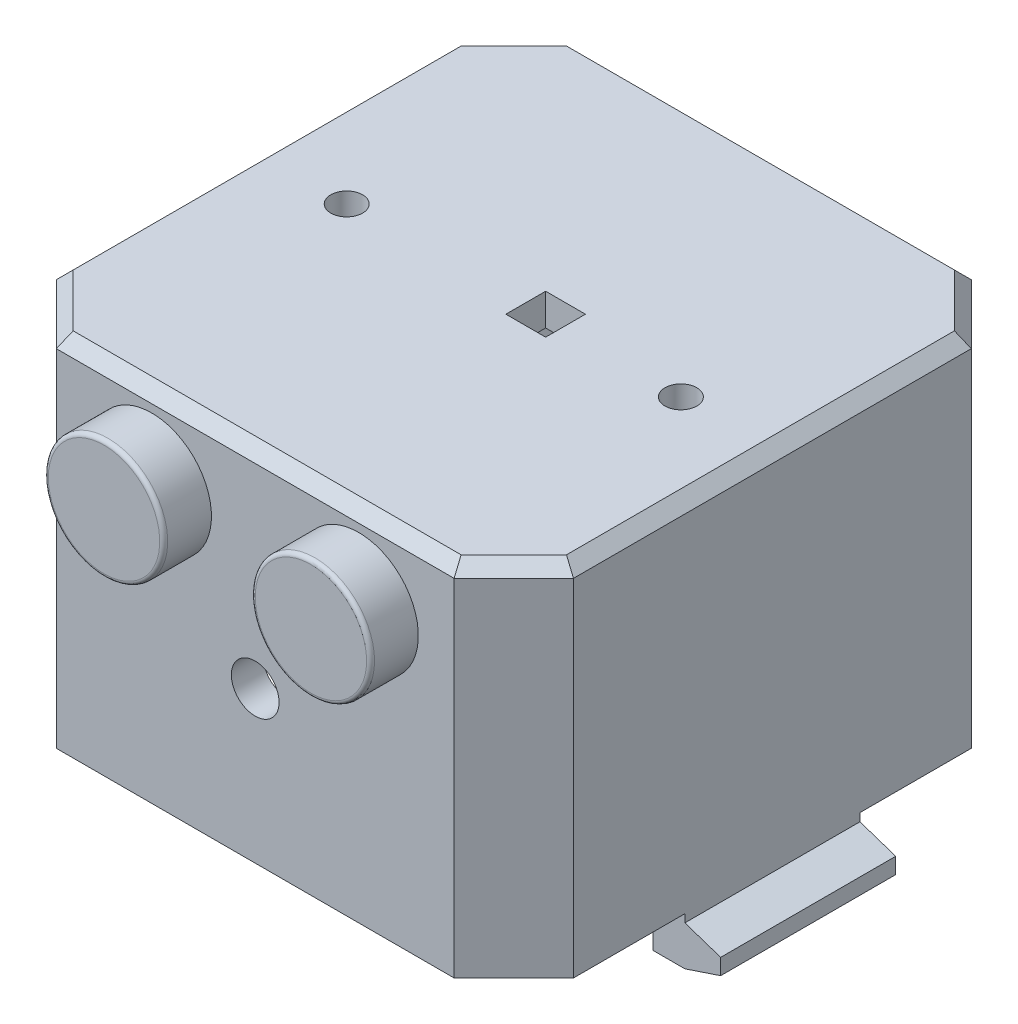
SolidWorks part; units mm, degrees
ref_plane "Alzado" through (0, 0, 0) normal (0, 0, 1) x (1, 0, 0)
ref_plane "Planta" through (0, 0, 0) normal (0, 1, 0) x (1, 0, 0)
ref_plane "Vista lateral" through (0, 0, 0) normal (1, 0, 0) x (0, 0, -1)
sketch "Croquis1" plane through (0, 0, 0) normal (0, 1, 0) x (1, 0, 0)
  line L1 (-25, -32.5) -> (25, -32.5)
  line L3 (-25, 32.5) -> (25, 32.5)
  line L5 (-25, -32.5) -> (25, 32.5) construction
  line L6 (-25, 32.5) -> (25, -32.5) construction
  line L10 (32.5, 25) -> (32.5, -25)
  line L11 (25, -32.5) -> (32.5, -25)
  line L12 (32.5, 25) -> (25, 32.5)
  line L13 (-32.5, 25) -> (-32.5, -25)
  line L14 (-32.5, -25) -> (-25, -32.5)
  line L15 (-32.5, 25) -> (-25, 32.5)
  point P0 (0, 0)
  point P10 (0, 32.5)
  dimension "D1" = 65
  dimension "D2" = 65
  dimension "D3" = 50
  dimension "D4" = 50
  dimension "D5" = 25
  dimension "D6" = 25
extrude "Saliente-Extruir1" add sketch "Croquis1" along normal blind 45
shell "Vaciado2" thickness 4 removed face at (0, 0, 0)
chamfer "Chaflán3" distance 1.5 angle 45 8 edges at (0, 45, -32.5) (32.5, 45, 0) (0, 45, 32.5) (-32.5, 45, 0) (-28.75, 45, 28.75) (28.75, 45, 28.75) (28.75, 45, -28.75) (-28.75, 45, -28.75)
sketch "Croquis2" plane through (0, 0, 32.5) normal (0, 0, 1) x (1, 0, 0)
  line L0 (0, 0) -> (0, 6.916) construction
  circle A0 centre (13, 35) radius 7.5
  circle A1 centre (-13, 35) radius 7.5
  dimension "D1" = 15
  dimension "D2" = 13
  dimension "D3" = 35
extrude "Saliente-Extruir2" add sketch "Croquis2" along normal blind 6
sketch "Croquis4" plane through (0, 0, 28.5) normal (0, 0, -1) x (-1, 0, 0)
  line L0 (0, 0) -> (0, 4.7403) construction
  line L1 (0, 0) -> (0, 6.916) construction
  circle A0 centre (-13, 35) radius 5
  circle A1 centre (13, 35) radius 5
  dimension "D1" = 10
extrude "Cortar-Extruir2" cut sketch "Croquis4" against normal blind 8
fillet "Redondeo1" radius 0.5 2 edges at (-20.5, 35, 38.5) (20.5, 35, 38.5)
sketch "Croquis5" plane through (0, 0, 32.5) normal (0, 0, 1) x (1, 0, 0)
  circle A0 centre (0, 19) radius 3
  dimension "D2" = 6
  dimension "D1" = 19
extrude "Cortar-Extruir3" cut sketch "Croquis5" against normal blind 10
sketch "Croquis13" plane through (0, 0, 36.5) normal (0, 0, -1) x (-1, 0, 0)
  circle A0 centre (-13, 35) radius 2.6
  circle A1 centre (13, 35) radius 2.6
  circle A2 centre (13, 35) radius 5
  circle A3 centre (-13, 35) radius 5
  dimension "D1" = 5.2
  dimension "D2" = 5.2
extrude "Saliente-Extruir8" add sketch "Croquis13" along normal blind 8
sketch "Croquis7" plane through (0, 0, 28.5) normal (0, 0, -1) x (-1, 0, 0)
  line L0 (23.3431, 0) -> (-23.3431, 0) construction
  line L1 (-13.58, 8.5) -> (-9.58, 8.5)
  line L2 (-13.58, 8.5) -> (-13.58, 12.5)
  line L3 (-13.58, 12.5) -> (-9.58, 12.5)
  line L4 (-9.58, 8.5) -> (-9.58, 12.5)
  line L5 (-13.58, 8.5) -> (-9.58, 12.5) construction
  line L6 (-13.58, 12.5) -> (-9.58, 8.5) construction
  line L8 (-13.58, 26) -> (-9.58, 26)
  line L9 (-13.58, 26) -> (-13.58, 30)
  line L10 (-13.58, 30) -> (-9.58, 30)
  line L11 (-9.58, 26) -> (-9.58, 30)
  line L12 (-13.58, 26) -> (-9.58, 30) construction
  line L13 (-13.58, 30) -> (-9.58, 26) construction
  line L14 (13.43, 12.5) -> (9.43, 8.5) construction
  line L15 (13.43, 8.5) -> (9.43, 12.5) construction
  line L16 (9.43, 8.5) -> (9.43, 12.5)
  line L17 (13.43, 12.5) -> (9.43, 12.5)
  line L18 (13.43, 8.5) -> (13.43, 12.5)
  line L19 (13.43, 8.5) -> (9.43, 8.5)
  line L20 (13.43, 30) -> (9.43, 26) construction
  line L21 (13.43, 26) -> (9.43, 30) construction
  line L22 (9.43, 26) -> (9.43, 30)
  line L23 (13.43, 30) -> (9.43, 30)
  line L24 (13.43, 26) -> (13.43, 30)
  line L25 (13.43, 26) -> (9.43, 26)
  point P0 (-11.58, 10.5)
  point P8 (-11.58, 28)
  point P13 (0, 0)
  point P15 (11.43, 10.5)
  point P16 (11.43, 28)
  point P20 (11.43, 10.5)
  point P25 (11.43, 28)
  point P26 (-11.58, 28)
  point P27 (11.43, 28)
  point P28 (11.43, 10.5)
  point P29 (-11.58, 10.5)
  dimension "D1" = 10.5
  dimension "D2" = 4
  dimension "D3" = 4
  dimension "D4" = 11.58
  dimension "D5" = 4
  dimension "D6" = 4
  dimension "D7" = 28
  dimension "D8" = 23.01
  dimension "D9" = 23.01
  dimension "D10" = 4
  dimension "D11" = 4
  dimension "D12" = 4
  dimension "D13" = 4
  dimension "D14" = 10.5
  dimension "D15" = 28
extrude "Saliente-Extruir3" add sketch "Croquis7" along normal blind 1
sketch "Croquis8" plane through (0, 0, 27.5) normal (0, 0, -1) x (-1, 0, 0)
  line L0 (0, 0) -> (0, 4.8013) construction
  line L1 (23.3431, 0) -> (-23.3431, 0) construction
  circle A0 centre (-11.505, 10.4893) radius 2
  circle A1 centre (-11.505, 27.9763) radius 2
  circle A2 centre (11.505, 10.4893) radius 2
  circle A3 centre (11.505, 27.9763) radius 2
  dimension "D1" = 4
  dimension "D2" = 4
  dimension "D3" = 23.01
  dimension "D4" = 23.01
extrude "Saliente-Extruir4" add sketch "Croquis8" along normal blind 1
sketch "Croquis9" plane through (0, 0, 26.5) normal (0, 0, -1) x (-1, 0, 0)
  circle A0 centre (-11.505, 27.9763) radius 1.6
  circle A1 centre (-11.505, 10.4893) radius 1.6
  circle A2 centre (11.505, 10.4893) radius 1.6
  circle A3 centre (11.505, 27.9763) radius 1.6
  dimension "D1" = 3.2
  dimension "D2" = 3.2
  dimension "D3" = 3.2
  dimension "D4" = 3.2
extrude "Cortar-Extruir5" cut sketch "Croquis9" against normal blind 2
sketch "Croquis12" plane through (0, 41, 0) normal (0, -1, 0) x (1, 0, 0)
  line L0 (0, 0) -> (-5.199, 0) construction
  line L1 (-21.9, -8.93) -> (21.9, -8.93) construction
  line L2 (-21.9, -8.93) -> (-21.9, 8.93) construction
  line L3 (-21.9, 8.93) -> (21.9, 8.93) construction
  line L4 (21.9, -8.93) -> (21.9, 8.93) construction
  line L5 (-21.9, -8.93) -> (21.9, 8.93) construction
  line L6 (-21.9, 8.93) -> (21.9, -8.93) construction
  line L7 (0, 0) -> (0, 4.1573) construction
  circle A0 centre (-20.65, 7.68) radius 0.8
  circle A1 centre (-20.65, 7.68) radius 1.15
  circle A2 centre (-20.65, -7.68) radius 1.15
  circle A3 centre (-20.65, -7.68) radius 0.8
  circle A4 centre (20.65, 7.68) radius 1.15
  circle A5 centre (20.65, 7.68) radius 0.8
  circle A6 centre (20.65, -7.68) radius 1.15
  circle A7 centre (20.65, -7.68) radius 0.8
  point P0 (0, 0)
  dimension "D6" = 1.6
  dimension "D4" = 2.3
  dimension "D1" = 43.8
  dimension "D2" = 17.86
  dimension "D3" = 1.25
  dimension "D7" = 1.25
extrude "Saliente-Extruir7" add sketch "Croquis12" along normal blind 6
sketch "Croquis14" plane through (0, 41, 0) normal (0, -1, 0) x (1, 0, 0)
  line L1 (-22.15, 6.43) -> (-19.15, 6.43)
  line L2 (-22.15, 6.43) -> (-22.15, 8.93)
  line L3 (-22.15, 8.93) -> (-19.15, 8.93)
  line L4 (-19.15, 6.43) -> (-19.15, 8.93)
  line L5 (-22.15, 6.43) -> (-19.15, 8.93) construction
  line L6 (-22.15, 8.93) -> (-19.15, 6.43) construction
  line L7 (-22.15, -8.93) -> (-19.15, -8.93)
  line L8 (-22.15, -8.93) -> (-22.15, -6.43)
  line L9 (-22.15, -6.43) -> (-19.15, -6.43)
  line L10 (-19.15, -8.93) -> (-19.15, -6.43)
  line L11 (-22.15, -8.93) -> (-19.15, -6.43) construction
  line L12 (-22.15, -6.43) -> (-19.15, -8.93) construction
  line L13 (19.15, 6.43) -> (22.15, 6.43)
  line L14 (19.15, 6.43) -> (19.15, 8.93)
  line L15 (19.15, 8.93) -> (22.15, 8.93)
  line L16 (22.15, 6.43) -> (22.15, 8.93)
  line L17 (19.15, 6.43) -> (22.15, 8.93) construction
  line L18 (19.15, 8.93) -> (22.15, 6.43) construction
  line L19 (19.15, -8.93) -> (22.15, -8.93)
  line L20 (19.15, -8.93) -> (19.15, -6.43)
  line L21 (19.15, -6.43) -> (22.15, -6.43)
  line L22 (22.15, -8.93) -> (22.15, -6.43)
  line L23 (19.15, -8.93) -> (22.15, -6.43) construction
  line L24 (19.15, -6.43) -> (22.15, -8.93) construction
  point P0 (-20.65, 7.68)
  point P6 (-20.65, -7.68)
  point P12 (20.65, 7.68)
  point P18 (20.65, -7.68)
  dimension "D1" = 3
  dimension "D2" = 2.5
  dimension "D3" = 3
  dimension "D4" = 2.5
  dimension "D5" = 3
  dimension "D6" = 2.5
  dimension "D7" = 3
  dimension "D8" = 2.5
extrude "Saliente-Extruir9" add sketch "Croquis14" along normal blind 5
sketch "Croquis15" plane through (-32.5, 0, 0) normal (-1, 0, 0) x (0, 0, 1)
  line L1 (-6, 40.5) -> (6, 40.5)
  line L2 (-6, 40.5) -> (-6, 32.5)
  line L3 (-6, 32.5) -> (6, 32.5)
  line L4 (6, 40.5) -> (6, 32.5)
  dimension "D1" = 8
  dimension "D2" = 12
  dimension "D3" = 3
  dimension "D4" = 19
extrude "Cortar-Extruir6" cut sketch "Croquis15" against normal blind 7
sketch "Croquis16" plane through (0, 0, -28.5) normal (0, 0, 1) x (1, 0, 0)
  line L2 (18.95, 6.05) -> (6.55, 6.05)
  line L3 (18.95, 6.05) -> (18.95, 18.45)
  line L4 (18.95, 18.45) -> (6.55, 18.45)
  line L5 (6.55, 6.05) -> (6.55, 18.45)
  line L6 (5.5, 5) -> (20, 5)
  line L7 (5.5, 5) -> (5.5, 19.5)
  line L8 (5.5, 19.5) -> (20, 19.5)
  line L9 (20, 5) -> (20, 19.5)
  line L10 (5.5, 5) -> (20, 19.5) construction
  line L11 (5.5, 19.5) -> (20, 5) construction
  line L12 (18.95, 6.05) -> (6.55, 18.45) construction
  line L13 (18.95, 18.45) -> (6.55, 6.05) construction
  point P0 (12.75, 12.25)
  point P4 (12.75, 12.25)
  dimension "D1" = 12.4
  dimension "D2" = 12.4
  dimension "D3" = 5
  dimension "D4" = 5
  dimension "D5" = 14.5
  dimension "D6" = 14.5
extrude "Saliente-Extruir10" add sketch "Croquis16" along normal blind 3
sketch "Croquis17" plane through (0, 0, -28.5) normal (0, 0, 1) x (1, 0, 0)
  circle A0 centre (12.75, 12.25) radius 5.5
  point P4 (12.75, 12.25)
  dimension "D1" = 11
extrude "Cortar-Extruir7" cut sketch "Croquis17" against normal through all
sketch "Croquis18" plane through (0, 0, 0) normal (0, -1, 0) x (1, 0, 0)
  line L1 (-32.5, 11) -> (-28.5, 11)
  line L2 (-32.5, 11) -> (-32.5, -11)
  line L3 (-32.5, -11) -> (-28.5, -11)
  line L4 (-28.5, 11) -> (-28.5, -11)
  line L5 (-32.5, -25) -> (-32.5, 25) construction
  line L6 (0, 0) -> (0, 8.739) construction
  line L7 (28.5, 11) -> (28.5, -11)
  line L8 (32.5, -11) -> (28.5, -11)
  line L9 (32.5, 11) -> (32.5, -11)
  line L10 (32.5, 11) -> (28.5, 11)
  point P4 (-28.5, 0)
  dimension "D1" = 4
  dimension "D2" = 22
extrude "Saliente-Extruir11" add sketch "Croquis18" along normal blind 6
sketch "Croquis19" plane through (0, 0, 11) normal (0, 0, 1) x (1, 0, 0)
  line L0 (-32.5, -3.5) -> (-37, -3.5) construction
  line L1 (-37, -2.5) -> (-37, -4.5)
  line L2 (-37, -2.5) -> (-32.5, -1)
  line L3 (-32.5, -6) -> (-32.5, 0)
  line L4 (-32.5, -6) -> (-32.5, -1)
  line L5 (-32.5, -6) -> (-37, -4.5)
  line L6 (0, 0) -> (0, 6.3616) construction
  line L7 (-25, 0) -> (25, 0) construction
  line L8 (32.5, -3.5) -> (37, -3.5) construction
  line L9 (32.5, -6) -> (37, -4.5)
  line L10 (32.5, -6) -> (32.5, -1)
  line L11 (32.5, -6) -> (32.5, 0)
  line L12 (37, -2.5) -> (32.5, -1)
  line L13 (37, -2.5) -> (37, -4.5)
  point P18 (-37, -3.5)
  line M6 (-32.5, 0) -> (-32.5, -6)
  dimension "D1" = 2
extrude "Saliente-Extruir13" add sketch "Croquis19" against normal blind 22 contours L5 L2 L1 M6 | L13 L12 L10 L9 region at (-34.4286, -3.5, 11) region at (34.4286, -3.5, 11)
sketch "Croquis20" plane through (0, 45, 0) normal (0, 1, 0) x (1, 0, 0)
  line L1 (6.0029, -2) -> (1.0029, -2)
  line L2 (6.0029, -2) -> (6.0029, 3)
  line L3 (6.0029, 3) -> (1.0029, 3)
  line L4 (1.0029, -2) -> (1.0029, 3)
  dimension "D1" = 5
  dimension "D2" = 5
  dimension "D3" = 2
extrude "Cortar-Extruir8" cut sketch "Croquis20" against normal blind 10
sketch "Croquis10" plane through (0, 45, 0) normal (0, 1, 0) x (1, 0, 0)
  line L0 (-31, 24.3787) -> (-31, -24.3787) construction
  line L1 (-31, -4) -> (-11, -4) construction
  line L2 (-31, -4) -> (-31, 4) construction
  line L3 (-31, 4) -> (-11, 4) construction
  line L4 (-11, -4) -> (-11, 4) construction
  line L5 (-31, -4) -> (-11, 4) construction
  line L6 (-31, 4) -> (-11, -4) construction
  line L7 (0, 0) -> (0, 7.307) construction
  line L8 (31, 4) -> (11, -4) construction
  line L9 (31, -4) -> (11, 4) construction
  line L10 (11, -4) -> (11, 4) construction
  line L11 (31, 4) -> (11, 4) construction
  line L12 (31, -4) -> (31, 4) construction
  line L13 (31, -4) -> (11, -4) construction
  circle A0 centre (-21, 0) radius 2
  circle A1 centre (21, 0) radius 2
  point P0 (-21, 0)
  point P14 (21, 0)
  dimension "D3" = 4
  dimension "D4" = 4
  dimension "D1" = 20
  dimension "D2" = 8
extrude "Cortar-Extruir10" cut sketch "Croquis10" against normal through all
